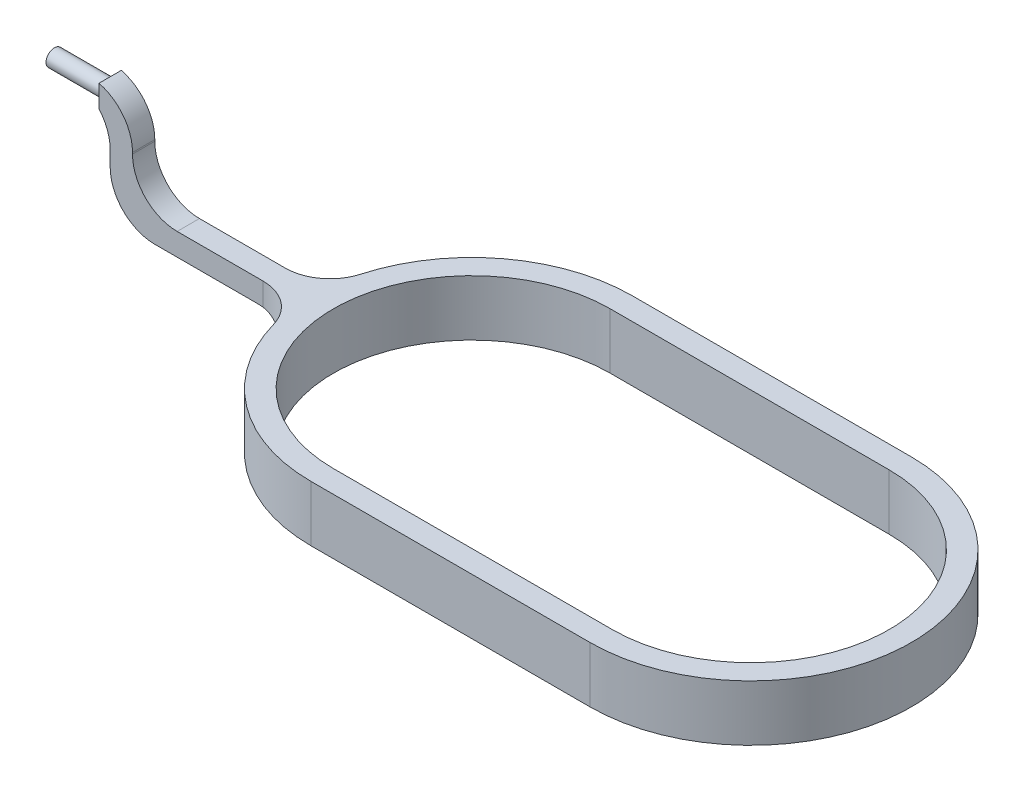
SolidWorks part; units mm, degrees
ref_plane "Front Plane" through (0, 0, 0) normal (0, 0, 1) x (1, 0, 0)
ref_plane "Top Plane" through (0, 0, 0) normal (0, 1, 0) x (1, 0, 0)
ref_plane "Right Plane" through (0, 0, 0) normal (1, 0, 0) x (0, 0, -1)
sketch "Sketch1" plane through (0, 0, 0) normal (0, 1, 0) x (1, 0, 0)
  line L0 (0, 0) -> (25, 0) construction
  line L1 (0, 12.4) -> (25, 12.4)
  line L2 (0, -12.4) -> (25, -12.4)
  line L3 (0, 0) -> (25, 0) construction
  line L4 (0, 14.4) -> (25, 14.4)
  line L5 (0, -14.4) -> (25, -14.4)
  arc A0 (0, 12.4) -> (0, -12.4) centre (0, 0) ccw
  arc A1 (25, -12.4) -> (25, 12.4) centre (25, 0) ccw
  arc A2 (0, 14.4) -> (0, -14.4) centre (0, 0) ccw
  arc A3 (25, -14.4) -> (25, 14.4) centre (25, 0) ccw
  point P3 (12.5, 0)
  point P10 (12.5, 0)
  dimension "D1" = 24.8
  dimension "D2" = 25
  dimension "D3" = 2
extrude "Boss-Extrude1" add sketch "Sketch1" along normal blind 5
sketch "Sketch4" plane through (0, 0, 0) normal (0, 0, 1) x (1, 0, 0)
  line L0 (-14.4, 5) -> (-14.4, 0) construction
  line L1 (-12.4, 5) -> (-29.4, 5)
  line L2 (-12.4, 5) -> (-12.4, 3)
  line L3 (-12.4, 3) -> (-29.4, 3)
  line L4 (-29.4, 5) -> (-29.4, 3)
  line L5 (0, 5) -> (0, 0) construction
  line L6 (-29.4, 3) -> (-31.4, 3)
  line L7 (-29.4, 3) -> (-29.4, 12)
  line L8 (-29.4, 12) -> (-31.4, 12)
  line L9 (-31.4, 3) -> (-31.4, 12)
  line L10 (-29.4, 13) -> (-32.4, 13)
  line L11 (-29.4, 13) -> (-29.4, 11)
  line L12 (-29.4, 11) -> (-32.4, 11)
  line L13 (-32.4, 13) -> (-32.4, 11)
  point P15 (-32.4, 12)
  dimension "D1" = 2
  dimension "D2" = 15
  dimension "D3" = 2
  dimension "D4" = 7
  dimension "D5" = 2
  dimension "D7" = 32.4
extrude "Boss-Extrude2" add sketch "Sketch4" along normal blind 1 and the other way blind 1 contours L10 L13 L12 L9 L8 L11 | L12 L7 L8 L9 | L7 L12 L9 L6 L4 | L1 L4 L3 L2 region at (-20.9, 4, 0) region at (-30.4, 7, 0) region at (-30.4, 11.5, 0) region at (-31.15, 12.25, 0)
sketch "Sketch5" plane through (-32.4, 0, 0) normal (-1, 0, 0) x (0, 0, 1)
  line L0 (-1, 11) -> (1, 11) construction
  line L1 (1, 13) -> (1, 11) construction
  circle A0 centre (0, 12) radius 0.75
  point P5 (0, 11)
  point P9 (1, 12)
  dimension "D1" = 1.5
extrude "Boss-Extrude3" add sketch "Sketch5" along normal blind 5
fillet "Fillet1" radius 4 7 edges at (-14.3652, 4, -1) (-14.3652, 4, 1) (-14.4, 3, 0) (-31.4, 3, 0) (-29.4, 5, 0) (-29.4, 13, 0) (-31.4, 11, 0)
